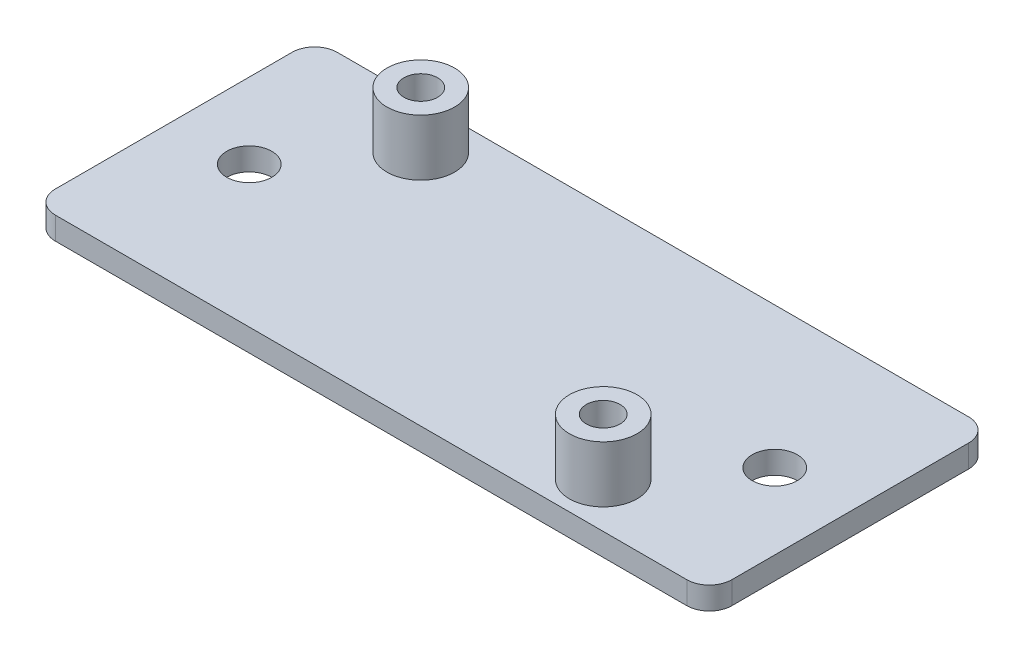
SolidWorks part; units mm, degrees
ref_plane "Спереди" through (0, 0, 0) normal (0, 0, 1) x (1, 0, 0)
ref_plane "Сверху" through (0, 0, 0) normal (0, 1, 0) x (1, 0, 0)
ref_plane "Справа" through (0, 0, 0) normal (1, 0, 0) x (0, 0, -1)
sketch "Эскиз1" plane through (0, 0, 0) normal (0, 1, 0) x (1, 0, 0)
  line L1 (0, 0) -> (60, 0)
  line L2 (0, 0) -> (0, -25)
  line L3 (0, -25) -> (60, -25)
  line L4 (60, 0) -> (60, -25)
  dimension "D1" = 25
  dimension "D2" = 60
extrude "Бобышка-Вытянуть1" add sketch "Эскиз1" along normal blind 2
sketch "Эскиз2" plane through (0, 2, 0) normal (0, 1, 0) x (1, 0, 0)
  line L0 (0, 0) -> (0, -25) construction
  line L1 (60, -25) -> (60, 0) construction
  line L2 (60, 0) -> (0, 0) construction
  line L3 (0, -25) -> (60, -25) construction
  circle A0 centre (13.41, -4) radius 3
  circle A1 centre (46.59, -21) radius 3
  dimension "D2" = 13.41
  dimension "D4" = 4
  dimension "D5" = 6
  dimension "D6" = 6
  dimension "D1" = 13.41
  dimension "D3" = 4
extrude "Бобышка-Вытянуть2" add sketch "Эскиз2" along normal blind 5
sketch "Эскиз3" plane through (0, 7, 0) normal (0, 1, 0) x (1, 0, 0)
  circle A0 centre (13.41, -4) radius 1.5
  circle A1 centre (46.59, -21) radius 1.5
  dimension "D1" = 3
  dimension "D2" = 3
extrude "Вырез-Вытянуть1" cut sketch "Эскиз3" against normal through all both and the other way through all
sketch "Эскиз4" plane through (0, 2, 0) normal (0, 1, 0) x (1, 0, 0)
  line L0 (0, -12.5) -> (60, -12.5) construction
  line L1 (0, 0) -> (0, -25) construction
  line L2 (60, -25) -> (60, 0) construction
  circle A0 centre (6.7, -12.5) radius 2
  circle A1 centre (53.3, -12.5) radius 2
  dimension "D1" = 4
  dimension "D2" = 4
  dimension "D3" = 6.7
  dimension "D4" = 6.7
extrude "Вырез-Вытянуть2" cut sketch "Эскиз4" against normal through all both and the other way through all
fillet "Скругление1" radius 2 1 edges at (0, 1, 0) type face fillet first side face at (30, 1, 0) second side face at (0, 1, 12.5)
fillet "Скругление2" radius 2 1 edges at (0, 1, 25) type face fillet first side face at (0, 1, 13.5) second side face at (30, 1, 25)
fillet "Скругление3" radius 2 1 edges at (60, 1, 25) type face fillet first side face at (31, 1, 25) second side face at (60, 1, 12.5)
fillet "Скругление4" radius 2 1 edges at (60, 1, 0) type face fillet first side face at (60, 1, 11.5) second side face at (31, 1, 0)
